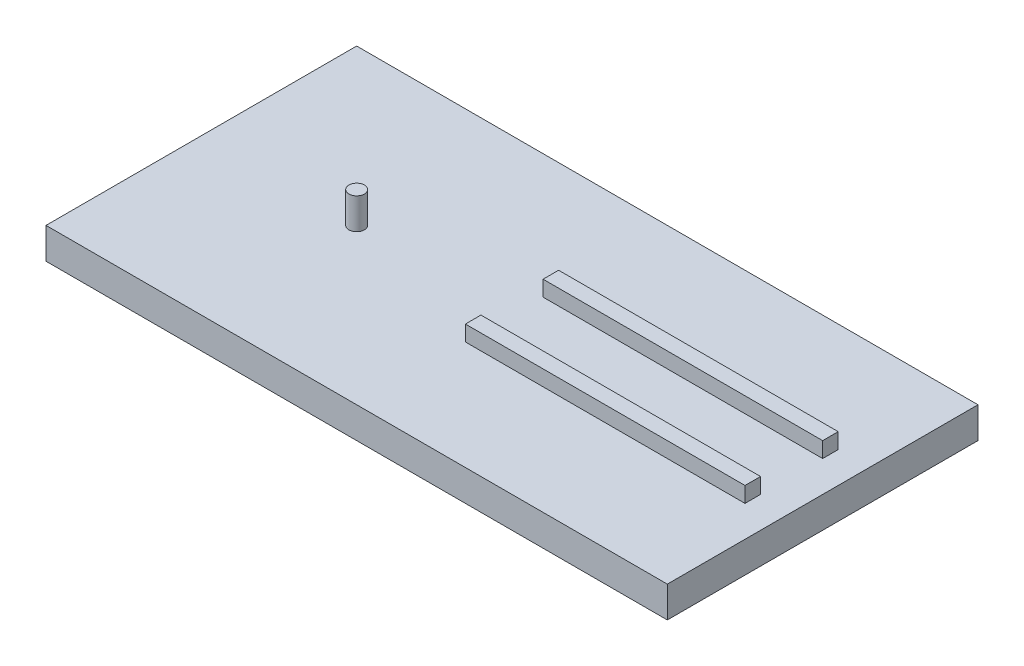
SolidWorks part; units mm, degrees
material "AISI 316 Annealed Stainless Steel Bar (SS)"
ref_plane "Front Plane" through (0, 0, 0) normal (0, 0, 1) x (1, 0, 0)
ref_plane "Top Plane" through (0, 0, 0) normal (0, 1, 0) x (1, 0, 0)
ref_plane "Right Plane" through (0, 0, 0) normal (1, 0, 0) x (0, 0, -1)
sketch "Sketch1" plane through (0, 0, 0) normal (0, 1, 0) x (1, 0, 0)
  line L1 (-100, -50) -> (100, -50)
  line L2 (-100, -50) -> (-100, 50)
  line L3 (-100, 50) -> (100, 50)
  line L4 (100, -50) -> (100, 50)
  line L5 (-100, -50) -> (100, 50) construction
  line L6 (-100, 50) -> (100, -50) construction
  point P0 (0, 0)
  dimension "D1" = 100
  dimension "D2" = 200
extrude "Boss-Extrude1" add sketch "Sketch1" along normal blind 10
sketch "Sketch2" plane through (0, 10, 0) normal (0, 1, 0) x (1, 0, 0)
  line L0 (100, -50) -> (100, 50) construction
  line L1 (0, 15) -> (90, 15)
  line L2 (0, 15) -> (0, 10)
  line L3 (0, 10) -> (90, 10)
  line L4 (90, 15) -> (90, 10)
  line L5 (0, 15) -> (90, 10) construction
  line L6 (0, 10) -> (90, 15) construction
  line L7 (0, -15) -> (90, -15)
  line L8 (0, -15) -> (0, -10)
  line L9 (0, -10) -> (90, -10)
  line L10 (90, -15) -> (90, -10)
  line L11 (0, -15) -> (90, -10) construction
  line L12 (0, -10) -> (90, -15) construction
  line L13 (100, 50) -> (-100, 50) construction
  line L14 (-100, -50) -> (100, -50) construction
  circle A0 centre (-50, 0) radius 2.5
  point P0 (45, 12.5)
  point P5 (45, -12.5)
  dimension "D1" = 5
  dimension "D2" = 5
  dimension "D3" = 90
  dimension "D4" = 10
  dimension "D5" = 35
  dimension "D6" = 35
  dimension "D7" = 50
extrude "Boss-Extrude2" add sketch "Sketch2" along normal blind 5 contours L9 L10 L7 L8 | L1 L4 L3 L2
extrude "Boss-Extrude3" add sketch "Sketch2<3>" along normal blind 10 contours A0
sketch "Sketch2<3>" plane through (0, 10, 0) normal (0, 1, 0) x (1, 0, 0) same geometry as "Sketch2"
